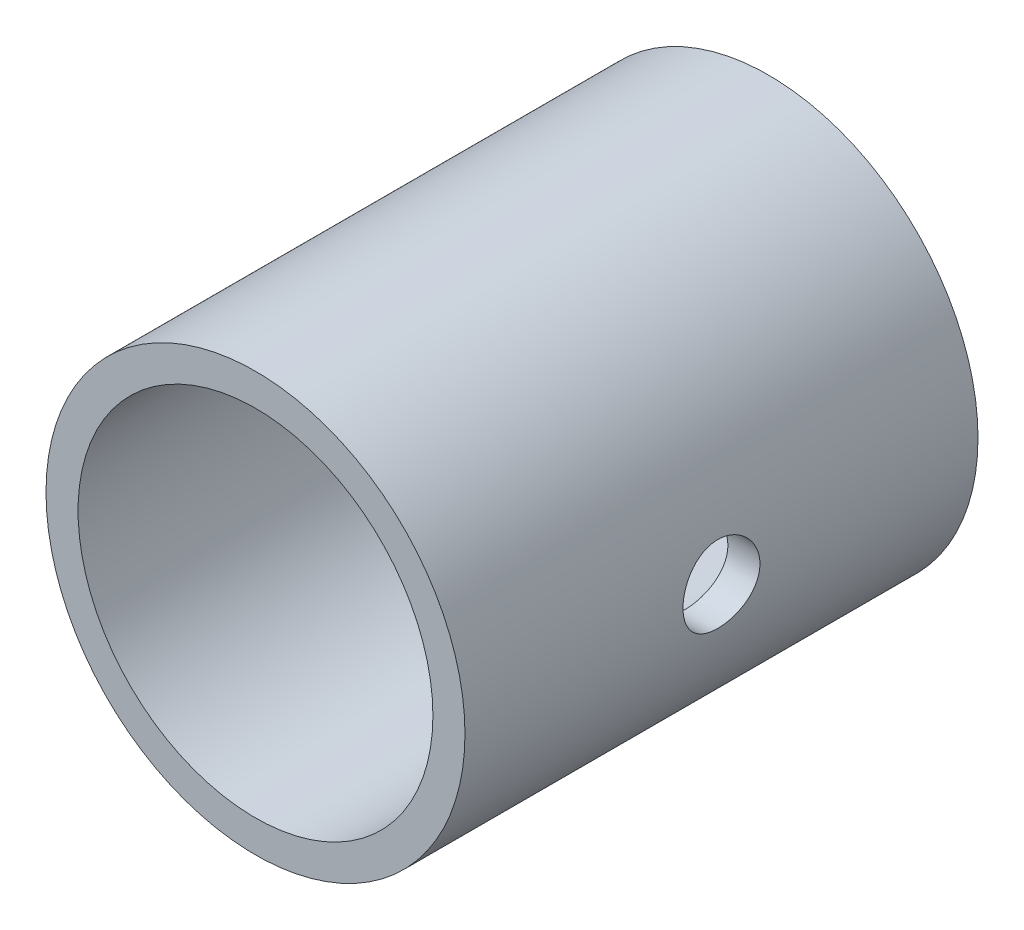
SolidWorks part; units mm, degrees
ref_plane "Front Plane" through (0, 0, 0) normal (0, 0, 1) x (1, 0, 0)
ref_plane "Top Plane" through (0, 0, 0) normal (0, 1, 0) x (1, 0, 0)
ref_plane "Right Plane" through (0, 0, 0) normal (1, 0, 0) x (0, 0, -1)
sketch "Sketch1" plane through (0, 0, 0) normal (0, 0, 1) x (1, 0, 0)
  circle A0 centre (0, 0) radius 4.9
  dimension "D1" = 9.8
extrude "Boss-Extrude1" add sketch "Sketch1" along normal blind 12
sketch "Sketch2" plane through (0, 0, 12) normal (0, 0, 1) x (1, 0, 0)
  circle A0 centre (0, 0) radius 4.15
  dimension "D1" = 8.3
extrude "Cut-Extrude1" cut sketch "Sketch2" against normal blind 15
sketch "Sketch3" plane through (0, 0, 0) normal (1, 0, 0) x (0, 0, -1)
  line L0 (-12, 0) -> (0, 0) construction
  line L1 (-12, 4.9) -> (-12, -4.9) construction
  line L2 (0, -4.9) -> (0, 4.9) construction
  circle A0 centre (-6, 0) radius 0.9
  dimension "D1" = 1.8
extrude "Cut-Extrude2" cut sketch "Sketch3" against normal through all both and the other way through all
